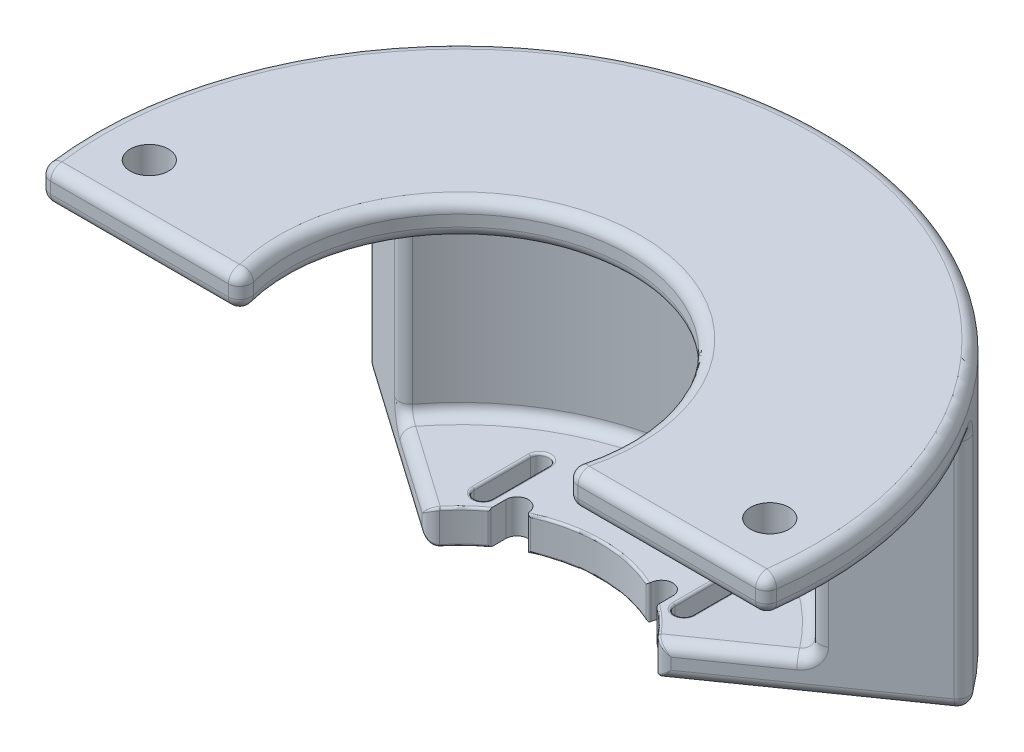
SolidWorks part; units mm, degrees
ref_plane "Front" through (0, 0, 0) normal (0, 0, 1) x (1, 0, 0)
ref_plane "Top" through (0, 0, 0) normal (0, 1, 0) x (1, 0, 0)
ref_plane "Right" through (0, 0, 0) normal (1, 0, 0) x (0, 0, -1)
sketch "Sketch1" plane through (0, 0, 0) normal (0, 1, 0) x (1, 0, 0)
  circle A0 centre (0, 0) radius 32.5
  circle A1 centre (0, 0) radius 15
  dimension "D1" = 30
  dimension "D2" = 65
extrude "Boss-Extrude1" add sketch "Sketch1" along normal blind 3
hole_wizard "M3 Clearance Hole1" positions "Sketch2" profile "Sketch3" hole size "M3" standard "ISO"
sketch "Sketch2" plane through (0, 3, 0) normal (0, 1, 0) x (1, 0, 0)
  line L0 (27.5, 0) -> (-27.5, 0) construction
  point P0 (27.5, 0)
  point P2 (-27.5, 0)
  dimension "D1" = 55
sketch "Sketch3" plane through (27.5, 3, 0) normal (1, 0, 0) x (0, 0, 1)
  line L0 (0, 0) -> (0, 11.1215)
  line L1 (0, 11.1215) -> (1.7, 10.1)
  line L2 (1.7, 10.1) -> (1.7, 0)
  line L5 (1.7, 0) -> (0, 0)
  line L10 (0, 11.1215) -> (-1.7, 10.1) construction
  line L11 (0, -6.35) -> (0, 107.95) construction
  dimension "Hole Dia." = 3.4
  dimension "Hole Depth" = 10.1
  dimension "Drill Angle" = 118
sketch "Sketch4" plane through (0, 0, 0) normal (0, -1, 0) x (1, 0, 0)
  line L1 (-36.5255, 5) -> (40.3726, 5)
  line L2 (-36.5255, 5) -> (-36.5255, 38.2404)
  line L3 (-36.5255, 38.2404) -> (40.3726, 38.2404)
  line L4 (40.3726, 5) -> (40.3726, 38.2404)
  dimension "D1" = 5
extrude "Cut-Extrude1" cut sketch "Sketch4" against normal through all
sketch "Sketch9" plane through (0, 0, 0) normal (0, -1, 0) x (1, 0, 0)
  line L0 (-18.4309, -12.9055) -> (-26.6224, -18.6412)
  line L1 (0, 15.3648) -> (0, -49.7612) construction
  line L2 (0, 0) -> (-18.4309, -12.9055) construction
  line L3 (18.4309, -12.9055) -> (26.6224, -18.6412)
  arc A0 (-32.1131, 5) -> (32.1131, 5) centre (0, 0) ccw construction
  arc A1 (-26.6224, -18.6412) -> (26.6224, -18.6412) centre (0, 0) ccw
  arc A2 (-18.4309, -12.9055) -> (18.4309, -12.9055) centre (0, 0) ccw
  dimension "D2" = 10
  dimension "D1" = 55
extrude "Boss-Extrude3" add sketch "Sketch9" along normal blind 21.76
sketch "Sketch10" plane through (0, -21.76, 0) normal (0, -1, 0) x (1, 0, 0)
  line L0 (0, -34.1752) -> (0, 13.1156) construction
  line L1 (-18.4309, -12.9055) -> (-10.2394, -7.1697)
  line L2 (18.4309, -12.9055) -> (10.2394, -7.1697)
  line L3 (26.6224, -18.6412) -> (18.4309, -12.9055)
  line L4 (-18.4309, -12.9055) -> (-26.6224, -18.6412)
  line L5 (26.6224, -18.6412) -> (18.4309, -12.9055)
  line L6 (-18.4309, -12.9055) -> (-26.6224, -18.6412)
  arc A0 (-18.4309, -12.9055) -> (18.4309, -12.9055) centre (0, 0) ccw construction
  arc A1 (-10.2394, -7.1697) -> (10.2394, -7.1697) centre (0, 0) ccw
  arc A3 (-26.6224, -18.6412) -> (26.6224, -18.6412) centre (0, 0) ccw
  arc A4 (-18.4309, -12.9055) -> (18.4309, -12.9055) centre (0, 0) ccw
  arc A5 (-26.6224, -18.6412) -> (26.6224, -18.6412) centre (0, 0) ccw
  dimension "D2" = 10
  dimension "D1" = 0
extrude "Boss-Extrude4" add sketch "Sketch10" against normal blind 3
sketch "Sketch11" plane through (0, -21.76, 0) normal (0, -1, 0) x (1, 0, 0)
  line L0 (0, 0) -> (0, -46.1012) construction
  line L1 (-8.9, -16) -> (-8.9, -11) construction
  line L2 (-9.7, -16) -> (-9.7, -11)
  line L3 (-8.1, -16) -> (-8.1, -11)
  line L4 (8.9, -16) -> (8.9, -11) construction
  line L5 (9.7, -16) -> (9.7, -11)
  line L6 (8.1, -16) -> (8.1, -11)
  line L7 (-6.4, -11.5) -> (-6.4, -8.5) construction
  line L8 (-7.4, -11.5) -> (-7.4, -8.5)
  line L9 (-5.4, -11.5) -> (-5.4, -8.5)
  line L10 (6.4, -11.5) -> (6.4, -8.5) construction
  line L11 (7.4, -11.5) -> (7.4, -8.5)
  line L12 (5.4, -11.5) -> (5.4, -8.5)
  arc A0 (-9.7, -16) -> (-8.1, -16) centre (-8.9, -16) ccw
  arc A1 (-8.1, -11) -> (-9.7, -11) centre (-8.9, -11) ccw
  arc A2 (9.7, -16) -> (8.1, -16) centre (8.9, -16) cw
  arc A3 (8.1, -11) -> (9.7, -11) centre (8.9, -11) cw
  arc A4 (-7.4, -11.5) -> (-5.4, -11.5) centre (-6.4, -11.5) ccw
  arc A5 (-5.4, -8.5) -> (-7.4, -8.5) centre (-6.4, -8.5) ccw
  arc A7 (7.4, -11.5) -> (5.4, -11.5) centre (6.4, -11.5) cw
  arc A8 (5.4, -8.5) -> (7.4, -8.5) centre (6.4, -8.5) cw
  point P6 (-8.9, -13.5)
  point P13 (8.9, -13.5)
  point P20 (-6.4, -10)
  point P27 (6.4, -10)
  dimension "D1" = 0.8
  dimension "D5" = 1
  dimension "D2" = 5
  dimension "D3" = 8.9
  dimension "D4" = 11
  dimension "D6" = 6.4
  dimension "D7" = 3
  dimension "D8" = 10
extrude "Cut-Extrude2" cut sketch "Sketch11" against normal up to next
fillet "Fillet1" radius 1 28 edges at (-22.5267, 0, -15.7734) (-14.3352, -18.76, -10.0376) (-10.2394, -20.26, -7.1697) (-18.4309, -21.76, -12.9055) (18.4309, -21.76, -12.9055) (10.2394, -20.26, -7.1697) (14.3352, -18.76, -10.0376) (22.5267, 0, -15.7734) (-18.4309, -9.38, -12.9055) (0, 0, -22.5) (18.4309, -9.38, -12.9055) (0, -18.76, -22.5) (23.1276, 0, 5) (23.1276, 3, 5) (0, -21.76, -32.5) (26.6224, -10.88, -18.6412) (31.6574, 0, -7.3524) (32.1131, 1.5, 5) (0, 3, -32.5) (-31.6574, 0, -7.3524) (-26.6224, -10.88, -18.6412) (-32.1131, 1.5, 5) (-23.1276, 3, 5) (-23.1276, 0, 5) (0, 0, -15) (-14.1421, 1.5, 5) (0, 3, -15) (14.1421, 1.5, 5)
fillet "Fillet2" radius 0.2 34 edges at (10.3176, -19.0796, -7.5506) (10.3176, -21.4404, -7.5506) (-10.3176, -21.4404, -7.5506) (-10.3176, -19.0796, -7.5506) (8.9, -18.76, -16.8) (9.7, -18.76, -13.5) (8.9, -18.76, -10.2) (-9.7, -18.76, -13.5) (-8.9, -18.76, -16.8) (-8.1, -18.76, -13.5) (-8.9, -21.76, -16.8) (-9.7, -21.76, -13.5) (-8.9, -21.76, -10.2) (8.9, -21.76, -10.2) (9.7, -21.76, -13.5) (8.9, -21.76, -16.8) (7.4, -20.26, -10.0742) (8.5815, -18.76, -9.0889) (8.5815, -21.76, -9.0889) (0, -21.76, -12.5) (-5.4, -20.26, -11.2734) (0, -18.76, -12.5) (5.4, -20.26, -11.2734) (-7.4, -20.26, -10.0742) (-8.5815, -21.76, -9.0889) (-8.5815, -18.76, -9.0889) (8.1, -18.76, -13.5) (-8.9, -18.76, -10.2) (-8.1, -21.76, -13.5) (8.1, -21.76, -13.5)
